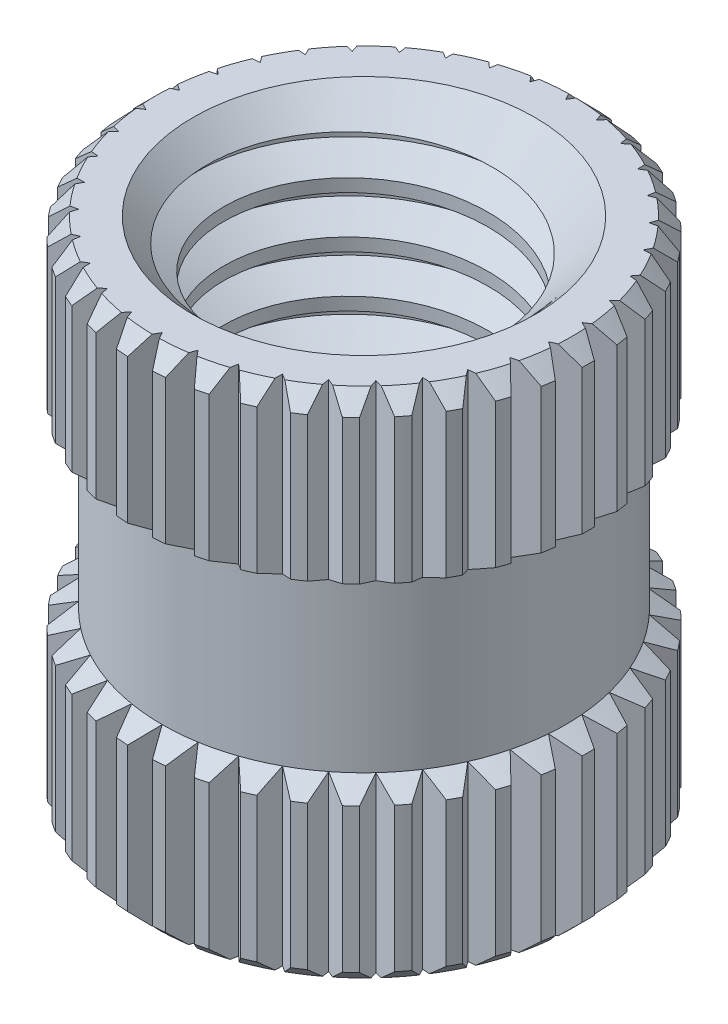
SolidWorks part; units mm, degrees
material "Brass"
ref_plane "Piano frontale" through (0, 0, 0) normal (0, 0, 1) x (1, 0, 0)
ref_plane "Piano superiore" through (0, 0, 0) normal (0, 1, 0) x (1, 0, 0)
ref_plane "Piano destro" through (0, 0, 0) normal (1, 0, 0) x (0, 0, -1)
sketch "Schizzo1" plane through (0, 0, 0) normal (0, 0, 1) x (1, 0, 0)
  line L0 (0, 0) -> (0, 18.7184) construction
  line L1 (0, 0) -> (0, 8)
  line L2 (0, 8) -> (-3.25, 8)
  line L3 (-3.5, 7.75) -> (-3.5, 5.5)
  line L4 (-3.5, 5.5) -> (-3.15, 5.2979)
  line L5 (-3.15, 5.2979) -> (-3.15, 2.7021)
  line L6 (-3.15, 2.7021) -> (-3.5, 2.5)
  line L7 (-3.5, 2.5) -> (-3.5, 0.25)
  line L8 (-3.25, 0) -> (0, 0)
  line L9 (-3.5, 0.25) -> (-3.25, 0)
  line L10 (-3.25, 8) -> (-3.5, 7.75)
  line L11 (0, 4) -> (-3.15, 4) construction
  point P6 (-3.5, 8)
  point P11 (-3.5, 0)
  dimension "D1" = 8
  dimension "D2" = 7
  dimension "D3" = 6.3
  dimension "D4" = 2.5
  dimension "D5" = 60
revolve "Rivoluzione1" add sketch "Schizzo1" angle 360 about L0
sketch "Schizzo4" plane through (0, 8, 0) normal (0, 1, 0) x (1, 0, 0)
  circle A0 centre (0, 0) radius 2.5
  dimension "D1" = 5
extrude "Taglio-Estrusione1" cut sketch "Schizzo4" against normal blind 10
thread "Filettatura1" pitch 0.8 method extrude trim with start face yes trim with end face yes profile "Profilo filettatura2" start angle 0, offset 1, length 0, pitch 0.8, diameter 5
ref_plane "Piano2" through (-2.5, 9, 0) normal (0, 0, 1) x (-1, 0, 0)
sketch "Profilo filettatura2" plane through (-2.5, 9, 0) normal (0, 0, 1) x (-1, 0, 0)
  line L0 (0, 0) -> (0, 0.8) construction
  line L11 (0, 0) -> (0, 0.7)
  line L12 (0, 0.7) -> (-0.433, 0.45)
  line L13 (-0.433, 0.45) -> (-0.433, 0.25)
  line L15 (-0.433, 0.25) -> (0, 0)
  line L17 (-0.433, 0.35) -> (0, 0.35) construction
  point P2 (0, 0)
  dimension "Pitch" = 0.8
  dimension "Profile_Angle" = 60
  dimension "Profile_Land" = 0.2
  dimension "Profile_Height" = 0.433
sketch "Schizzo10" plane through (0, 0, 0) normal (0, 0, 1) x (1, 0, 0)
  line L0 (0, 0) -> (0, 8.3294) construction
  line L1 (-3.667, 9) -> (-1.967, 7.3)
  line L2 (-1.967, 7.3) -> (-1.967, 9)
  line L4 (-1.967, 9) -> (-3.667, 9)
  line L6 (3.25, 8) -> (-3.25, 8) construction
  line L8 (-2.067, 7.95) -> (-2.067, 7.75) construction
  line L9 (-3.15, 4) -> (3.15, 4) construction
  line L10 (-3.15, 5.2979) -> (-3.15, 2.7021) construction
  line L11 (3.15, 2.7021) -> (3.15, 5.2979) construction
  line L12 (-1.967, 0.7) -> (-1.967, -1)
  line L13 (-3.667, -1) -> (-1.967, 0.7)
  line L14 (-1.967, -1) -> (-3.667, -1)
  dimension "D1" = 45
  dimension "D2" = 0.7
  dimension "D3" = 0.1
  dimension "D4" = 1
revolve "Taglia-Rivoluzione3" cut sketch "Schizzo10" angle 360 about L0
sketch "Schizzo12" plane through (0, 8, 0) normal (0, 1, 0) x (1, 0, 0)
  line L0 (0, 0) -> (0, 3.8607) construction
  line L1 (0, 3.15) -> (-0.4, 3.8607)
  line L2 (-0.4, 3.8607) -> (0.4, 3.8607)
  line L3 (0.4, 3.8607) -> (0, 3.15)
  circle A0 centre (0, 0) radius 3.5 construction
  circle A1 centre (0, 0) radius 3.15 construction
  dimension "D1" = 0.3607
  dimension "D2" = 0.8
extrude "Taglio-Estrusione2" cut sketch "Schizzo12" against normal through all
pattern_circular "RipetizioneCircolare1" count 38 over 360 about axis through (0, 8, 0) along (0, 1, 0) of "Taglio-Estrusione2"
